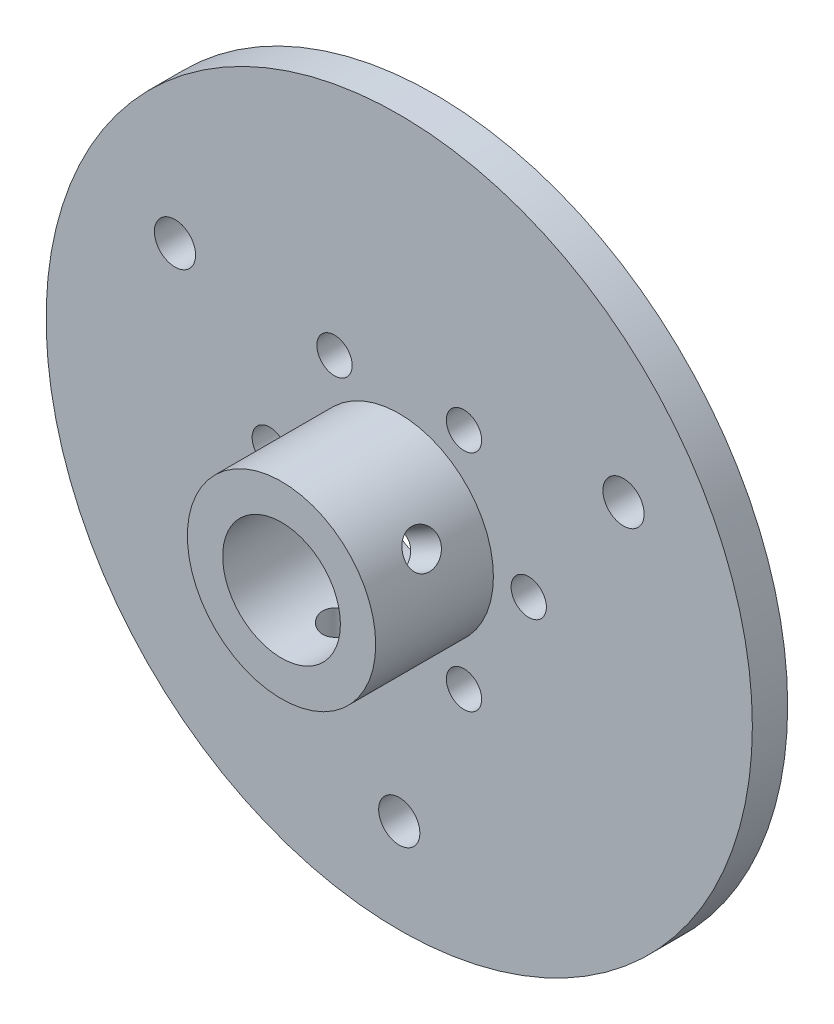
SolidWorks part; units mm, degrees
material "1060 Alloy"
ref_plane "Front Plane" through (0, 0, 0) normal (0, 0, 1) x (1, 0, 0)
ref_plane "Top Plane" through (0, 0, 0) normal (0, 1, 0) x (1, 0, 0)
ref_plane "Right Plane" through (0, 0, 0) normal (1, 0, 0) x (0, 0, -1)
sketch "Sketch2" plane through (0, 0, 0) normal (0, 0, 1) x (1, 0, 0)
  circle A0 centre (0, 0) radius 5
  circle A2 centre (0, 0) radius 22 construction
  circle A3 centre (0, 0) radius 30
  circle A4 centre (0, -22) radius 1.75
  circle A5 centre (-19.0526, 11) radius 1.75
  circle A6 centre (19.0526, 11) radius 1.75
  point P13 (0, 0)
  dimension "D1" = 3
  dimension "D2" = 44
  dimension "D3" = 3.5
  dimension "D4" = 10
  dimension "D5" = 60
extrude "Boss-Extrude1" add sketch "Sketch2" along normal blind 3
sketch "Sketch3" plane through (0, 0, 3) normal (0, 0, 1) x (1, 0, 0)
  circle A0 centre (0, 0) radius 8
  circle A1 centre (0, 0) radius 5
  dimension "D1" = 16
extrude "Boss-Extrude2" add sketch "Sketch3" along normal blind 10
sketch "Sketch4" plane through (0, 0, 3) normal (0, 0, 1) x (1, 0, 0)
  line L0 (0, 0) -> (-17.8949, 30.9948) construction
  line L1 (0, 0) -> (0, 33.1815) construction
  line L2 (0, 0) -> (16.5859, 28.7276) construction
  circle A9 centre (0, 0) radius 11
  circle A10 centre (-5.5, 9.5263) radius 1.5
  circle A11 centre (11, 0) radius 1.5
  circle A12 centre (-5.5, -9.5263) radius 1.5
  circle A14 centre (5.5, 9.5263) radius 1.5
  circle A15 centre (5.5, -9.5263) radius 1.5
  circle A16 centre (-11, 0) radius 1.5
  point P11 (0, 0)
  point P12 (0, 0)
  point P13 (0, 0)
  point P24 (0, 0)
  dimension "D1" = 3
  dimension "D2" = 3
  dimension "D4" = 22
  dimension "D3" = 30
  dimension "D5" = 2
  dimension "D6" = 30
extrude "Cut-Extrude2" cut sketch "Sketch4" against normal through all contours A12 | A11 | A10 | A16 | A14 | A15
sketch "Sketch12" plane through (0, 0, 0) normal (0, 1, 0) x (1, 0, 0)
  circle A0 centre (0, -8) radius 1.5
  dimension "D1" = 3
  dimension "D2" = 8
extrude "Cut-Extrude3" cut sketch "Sketch12" against normal blind 11.4938
pattern_circular "CirPattern1" count 3 every 120 about axis through (0, 0, 13) along (0, 0, 1) of "Cut-Extrude3"
